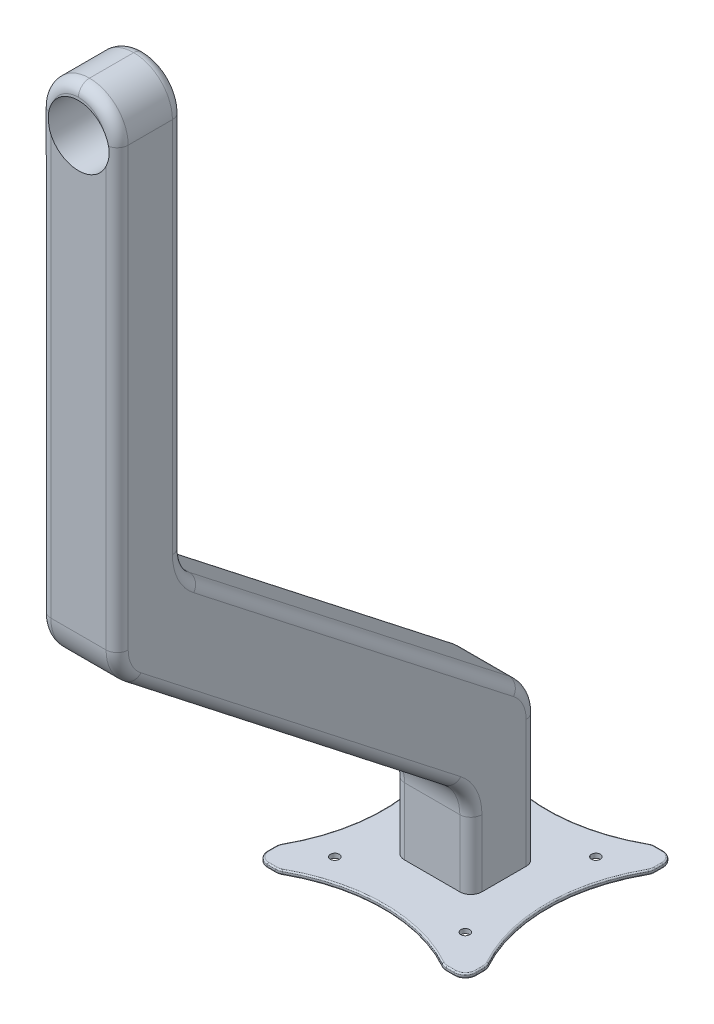
SolidWorks part; units mm, degrees
material "1060 Alloy"
ref_plane "Front" through (0, 0, 0) normal (0, 0, 1) x (1, 0, 0)
ref_plane "Top" through (0, 0, 0) normal (0, 1, 0) x (1, 0, 0)
ref_plane "Right" through (0, 0, 0) normal (1, 0, 0) x (0, 0, -1)
sketch "Sketch1" plane through (0, 0, 0) normal (0, 1, 0) x (1, 0, 0)
  line L0 (0, 47.3) -> (0, 0) construction
  line L1 (-60, 60) -> (-47.3, 60)
  line L2 (-60, 60) -> (-60, 47.3)
  line L3 (-60, -60) -> (-47.3, -60)
  line L4 (60, 60) -> (60, 47.3)
  line L5 (-60, 60) -> (60, -60) construction
  line L6 (-60, -60) -> (60, 60) construction
  line L7 (47.3, -60) -> (60, -60)
  line L8 (-37.5, 37.5) -> (37.5, 37.5) construction
  line L9 (-37.5, 37.5) -> (-37.5, -37.5) construction
  line L10 (-37.5, -37.5) -> (37.5, -37.5) construction
  line L11 (37.5, 37.5) -> (37.5, -37.5) construction
  line L12 (-37.5, 37.5) -> (37.5, -37.5) construction
  line L13 (-37.5, -37.5) -> (37.5, 37.5) construction
  line L14 (60, -47.3) -> (60, -60)
  line L15 (47.3, 60) -> (60, 60)
  line L16 (-60, -47.3) -> (-60, -60)
  arc A0 (-47.3, 60) -> (47.3, 60) centre (0, 141.7323) ccw
  circle A1 centre (-37.5, 37.5) radius 2.5527
  circle A2 centre (-37.5, -37.5) radius 2.5527
  circle A3 centre (37.5, -37.5) radius 2.5527
  circle A4 centre (37.5, 37.5) radius 2.5527
  arc A5 (60, 47.3) -> (60, -47.3) centre (141.7323, 0) ccw
  arc A6 (47.3, -60) -> (-47.3, -60) centre (0, -141.7323) ccw
  arc A7 (-60, -47.3) -> (-60, 47.3) centre (-141.7323, 0) ccw
  point P0 (0, 0)
  point P31 (0, 0)
  dimension "D3" = 5.1054
  dimension "D7" = 12.7
  dimension "D1" = 120
  dimension "D4" = 75
  dimension "D5" = 75
  dimension "D6" = 12.7
  dimension "D8" = 4
extrude "Boss-Extrude1" add sketch "Sketch1" along normal blind 2.54
fillet "Fillet1" radius 6.35 12 edges at (-60, 1.27, -47.3) (-60, 1.27, -60) (-47.3, 1.27, -60) (47.3, 1.27, -60) (60, 1.27, -60) (60, 1.27, -47.3) (60, 1.27, 47.3) (60, 1.27, 60) (47.3, 1.27, 60) (-47.3, 1.27, 60) (-60, 1.27, 60) (-60, 1.27, 47.3)
sketch "Sketch3" plane through (0, 0, 0) normal (1, 0, 0) x (0, 0, -1)
  line L0 (0, 2.54) -> (0, 70.6896) construction
  line L1 (45.8895, 2.54) -> (-45.8895, 2.54) construction
  line L2 (0, 70.6896) -> (-203.2, 229.4468) construction
  line L3 (-203.2, 229.4468) -> (-203.2, 497.84) construction
  line L4 (19.05, 2.54) -> (19.05, 88.0391)
  line L5 (-19.05, 2.54) -> (-19.05, 53.34)
  line L6 (19.05, 88.0391) -> (-184.15, 246.7964)
  line L7 (-19.05, 53.34) -> (-222.25, 212.0972)
  line L8 (-184.15, 246.7964) -> (-184.15, 497.84)
  line L9 (-222.25, 212.0972) -> (-222.25, 497.84)
  line L10 (-222.25, 229.4468) -> (-222.25, 497.84) construction
  line L11 (19.05, 2.54) -> (19.05, 70.6896) construction
  line L12 (15.6378, 90.705) -> (-187.5622, 249.4623) construction
  line L13 (-19.05, 2.54) -> (-19.05, 70.6896) construction
  line L14 (-15.6378, 50.6741) -> (-218.8378, 209.4313) construction
  line L15 (-184.15, 229.4468) -> (-184.15, 497.84) construction
  line L16 (-184.15, 497.84) -> (-222.25, 497.84)
  line L17 (19.05, 2.54) -> (-19.05, 2.54)
  dimension "D1" = 495.3
  dimension "D8" = 203.2
  dimension "D9" = 128
  dimension "D10" = 50.8
  dimension "D2" = 19.05
  dimension "D3" = 19.05
  dimension "D4" = 25.4
  dimension "D5" = 25.4
  dimension "D6" = 19.05
  dimension "D7" = 19.05
extrude "Boss-Extrude2" add sketch "Sketch3" along normal mid plane 44.45 separate body
sketch "Sketch4" plane through (0, 0, 184.15) normal (0, 0, -1) x (-1, 0, 0)
  line L0 (0, 497.84) -> (0, 472.44) construction
  line L1 (-22.225, 497.84) -> (22.225, 497.84) construction
  circle A0 centre (0, 472.44) radius 17.4625
  dimension "D1" = 34.925
  dimension "D2" = 25.4
extrude "Cut-Extrude1" cut sketch "Sketch4" against normal through all
fillet "Fillet2" radius 22.225 2 edges at (-22.225, 497.84, 203.2) (22.225, 497.84, 203.2)
fillet "Fillet3" radius 25.4 4 edges at (0, 53.34, 19.05) (0, 88.0391, -19.05) (0, 246.7964, 184.15) (0, 212.0972, 222.25)
fillet "Fillet4" radius 6.35 24 edges at (-22.225, 21.7458, 19.05) (-22.225, 52.0862, 21.6206) (-22.225, 132.7186, 120.65) (-22.225, 213.351, 219.6794) (-22.225, 350.0503, 222.25) (-15.7154, 491.3304, 222.25) (15.7154, 491.3304, 222.25) (22.225, 21.7458, 19.05) (22.225, 52.0862, 21.6206) (22.225, 132.7186, 120.65) (22.225, 213.351, 219.6794) (22.225, 39.0954, -19.05) (22.225, 86.7854, -16.4794) (22.225, 167.4178, 82.55) (22.225, 248.0502, 181.5794) (-22.225, 39.0954, -19.05) (-22.225, 86.7854, -16.4794) (-22.225, 167.4178, 82.55) (-22.225, 248.0502, 181.5794) (-22.225, 367.3999, 184.15) (-15.7154, 491.3304, 184.15) (15.7154, 491.3304, 184.15) (22.225, 350.0503, 222.25) (22.225, 367.3999, 184.15)
fillet "Fillet5" radius 0.762 48 edges at (47.3814, 2.54, -59.7967) (51.3126, 2.54, -60) (58.1401, 2.54, -58.1401) (60, 2.54, -51.3126) (59.7967, 2.54, -47.3814) (47.3, 2.54, 0) (59.7967, 2.54, 47.3814) (60, 2.54, 51.3126) (58.1401, 2.54, 58.1401) (51.3126, 2.54, 60) (47.3814, 2.54, 59.7967) (0, 2.54, 47.3) (-47.3814, 2.54, 59.7967) (-51.3126, 2.54, 60) (-58.1401, 2.54, 58.1401) (-60, 2.54, 51.3126) (-59.7967, 2.54, 47.3814) (-47.3, 2.54, 0) (-59.7967, 2.54, -47.3814) (-60, 2.54, -51.3126) (-58.1401, 2.54, -58.1401) (-51.3126, 2.54, -60) (-47.3814, 2.54, -59.7967) (47.3814, 0, -59.7967) (51.3126, 0, -60) (58.1401, 0, -58.1401) (60, 0, -51.3126) (59.7967, 0, -47.3814) (47.3, 0, 0) (59.7967, 0, 47.3814) (60, 0, 51.3126) (58.1401, 0, 58.1401) (51.3126, 0, 60) (47.3814, 0, 59.7967) (0, 0, 47.3) (-47.3814, 0, 59.7967) (-51.3126, 0, 60) (-58.1401, 0, 58.1401) (-60, 0, 51.3126) (-59.7967, 0, 47.3814) (-47.3, 0, 0) (-59.7967, 0, -47.3814) (-60, 0, -51.3126) (-58.1401, 0, -58.1401) (-51.3126, 0, -60) (-47.3814, 0, -59.7967) (0, 2.54, -47.3) (0, 0, -47.3)
